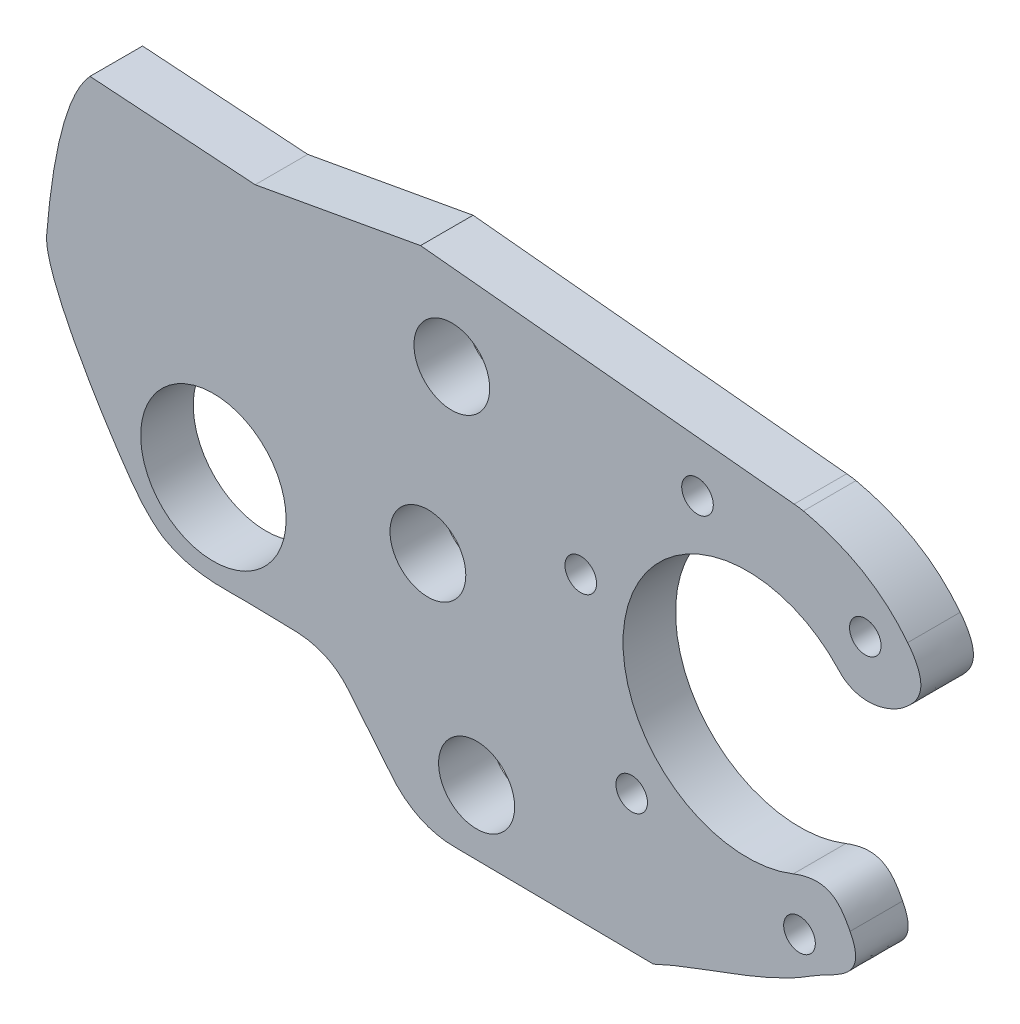
SolidWorks part; units mm, degrees
ref_plane "Front Plane" through (0, 0, 0) normal (0, 0, 1) x (1, 0, 0)
ref_plane "Top Plane" through (0, 0, 0) normal (0, 1, 0) x (1, 0, 0)
ref_plane "Right Plane" through (0, 0, 0) normal (1, 0, 0) x (0, 0, -1)
sketch "Sketch1" plane through (0, 0, 0) normal (0, 0, 1) x (1, 0, 0)
  line L1 (388.9371, 591.8019) -> (317.8384, 598.8518)
  line L2 (317.8384, 598.8518) -> (286.3759, 593.1514)
  line L3 (286.3759, 593.1514) -> (254.9413, 595.2929)
  line L4 (284.7215, 523.5997) -> (294.3118, 523.3986)
  line L5 (304.1649, 518.6915) -> (313.1736, 507.7735)
  line L6 (324.4499, 502.9891) -> (362.1482, 502.591)
  circle A0 centre (278.4237, 540.941) radius 13.8353
  circle A1 centre (319.2404, 548.8394) radius 7.2131
  circle A2 centre (328.5125, 515.2834) radius 7.2356
  circle A3 centre (323.7939, 581.8816) radius 7.2051
  circle A4 centre (402.4754, 576.7164) radius 3.0029
  circle A5 centre (370.5463, 583.9478) radius 3.0065
  circle A6 centre (348.3294, 559.9053) radius 3.0094
  circle A7 centre (358.0274, 528.6384) radius 3.0029
  circle A9 centre (389.9536, 521.3983) radius 3.0113
  circle A10 centre (0, 0) radius 10
  arc A12 (397.4617, 568.6354) -> (388.7679, 530.7766) centre (380.0009, 552.7175) ccw
  spline S1 degree 3 poles (397.4617, 568.6354) (400.9309, 564.9117) (406.4856, 566.1744) (409.7602, 568.6776) knots 0.041667 0.041667 0.041667 0.041667 0.083333 0.083333 0.083333 0.083333
  spline S2 degree 3 poles (409.7602, 568.6776) (413.0645, 571.2036) (414.7605, 574.3926) (410.5387, 579.7716) knots 0.083333 0.083333 0.083333 0.083333 0.125 0.125 0.125 0.125
  spline S3 degree 3 poles (410.5387, 579.7716) (405.594, 586.0719) (398.9165, 589.7078) (390.7024, 591.5464) knots 0.125 0.125 0.125 0.125 0.166667 0.166667 0.166667 0.166667
  spline S4 degree 3 poles (390.7024, 591.5464) (390.1702, 591.6655) (389.4989, 591.7468) (388.9371, 591.8019) knots 0.166667 0.166667 0.166667 0.166667 0.208333 0.208333 0.208333 0.208333
  spline S5 degree 3 poles (254.9413, 595.2929) (249.749, 589.6403) (247.5763, 576.1381) (246.6964, 565.0014) knots 0.333333 0.333333 0.333333 0.333333 0.375 0.375 0.375 0.375
  spline S6 degree 3 poles (246.6964, 565.0014) (246.2536, 559.3969) (253.8266, 545.9237) (260.2361, 536.2788) knots 0.375 0.375 0.375 0.375 0.416667 0.416667 0.416667 0.416667
  spline S7 degree 3 poles (260.2361, 536.2788) (261.9315, 533.7276) (265.3965, 528.2241) (269.3831, 526.0001) knots 0.416667 0.416667 0.416667 0.416667 0.458333 0.458333 0.458333 0.458333
  spline S8 degree 3 poles (269.3831, 526.0001) (274.7125, 523.027) (280.9349, 523.6791) (284.7215, 523.5997) knots 0.458333 0.458333 0.458333 0.458333 0.5 0.5 0.5 0.5
  spline S9 degree 3 poles (294.3118, 523.3986) (298.656, 523.1896) (301.8697, 521.53) (304.1649, 518.6915) knots 0.541667 0.541667 0.541667 0.541667 0.583333 0.583333 0.583333 0.583333
  spline S10 degree 3 poles (313.1736, 507.7735) (316.1604, 504.7059) (319.8516, 502.9821) (324.4499, 502.9891) knots 0.625 0.625 0.625 0.625 0.666667 0.666667 0.666667 0.666667
  spline S11 degree 3 poles (362.1482, 502.591) (370.3987, 506.5747) (383.2456, 509.8601) (391.8953, 515.4769) knots 0.708333 0.708333 0.708333 0.708333 0.75 0.75 0.75 0.75
  spline S12 degree 3 poles (391.8953, 515.4769) (396.6269, 518.5494) (403.2187, 519.6191) (399.5807, 526.7157) knots 0.75 0.75 0.75 0.75 0.791667 0.791667 0.791667 0.791667
  spline S13 degree 3 poles (399.5807, 526.7157) (397.6964, 530.3909) (395.5139, 533.4064) (388.7679, 530.7766) knots 0.791667 0.791667 0.791667 0.791667 0.833333 0.833333 0.833333 0.833333
  dimension "D1" = 27.6706
  dimension "D2" = 14.4712
  dimension "D3" = 14.4262
  dimension "D4" = 14.4101
  dimension "D5" = 6.0188
  dimension "D6" = 6.0129
  dimension "D7" = 6.0058
  dimension "D8" = 6.0058
  dimension "D9" = 6.0226
extrude "Boss-Extrude3" add sketch "Sketch1" along normal blind 10 contours A0 | A1 | A3 | A2 | A7 | A9 | A6 | A5 | A4 | L2 L3 S5 S6 S7 S8 L4 S9 L5 S10 L6 S11 S12 S13 A12 S1 S2 S3 S4 L1 region at (278.4237, 540.941, 0) region at (319.2404, 548.8394, 0) region at (328.5125, 515.2834, 0) region at (323.7939, 581.8816, 0) region at (402.4754, 576.7164, 0) region at (370.5463, 583.9478, 0) region at (348.3294, 559.9053, 0) region at (358.0274, 528.6384, 0) region at (389.9536, 521.3983, 0)
scale "Scale6" scale about origin uniform scaling yes scale factor 0.75
